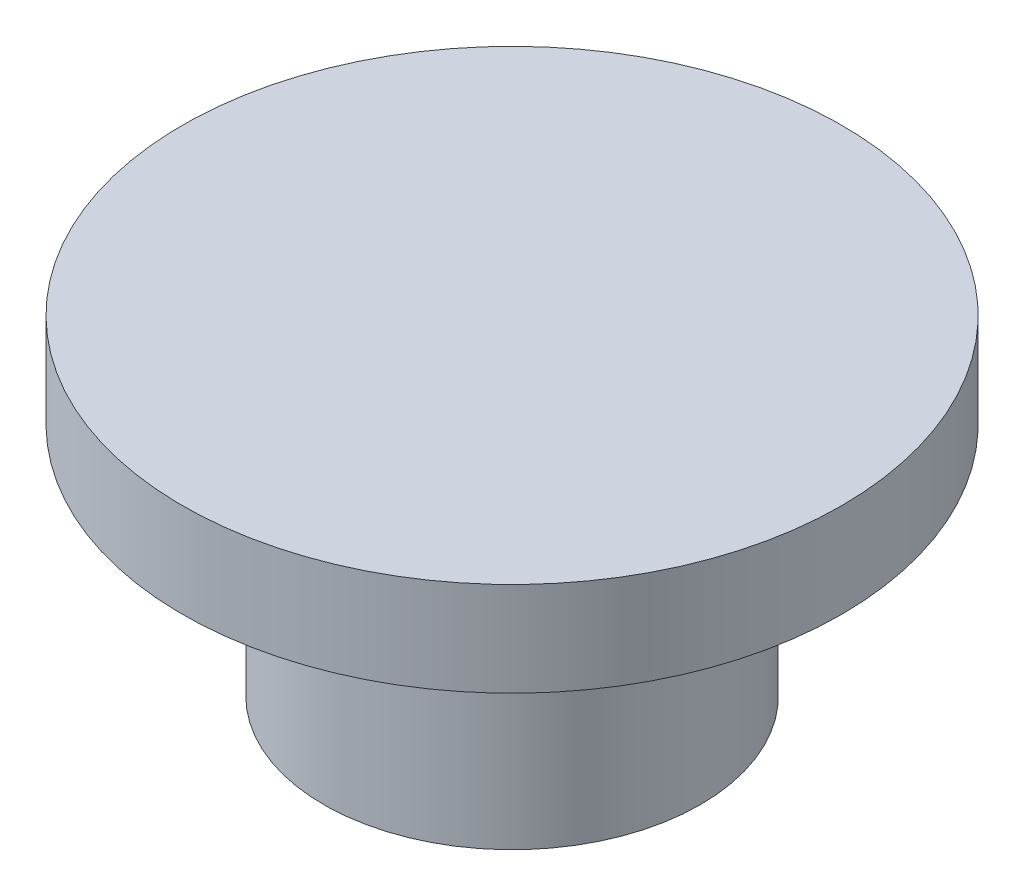
SolidWorks part; units mm, degrees
ref_plane "Front Plane" through (0, 0, 0) normal (0, 0, 1) x (1, 0, 0)
ref_plane "Top Plane" through (0, 0, 0) normal (0, 1, 0) x (1, 0, 0)
ref_plane "Right Plane" through (0, 0, 0) normal (1, 0, 0) x (0, 0, -1)
sketch "Sketch1" plane through (0, 0, 0) normal (0, 0, 1) x (1, 0, 0)
  line L0 (0, 35) -> (35, 35)
  line L1 (35, 35) -> (35, 25)
  line L2 (35, 25) -> (20, 25)
  line L3 (20, 25) -> (20, 0)
  line L6 (20, 0) -> (0, 0)
  line L7 (0, 0) -> (0, 35)
  point P3 (20, 0)
  point P10 (0, 0)
  dimension "D1" = 35
  dimension "D2" = 20
  dimension "D3" = 35
  dimension "D4" = 10
revolve "Revolve1" add sketch "Sketch1" angle 360 about L7
shell "Shell1" thickness 5 removed face at (20, 0, 0)
